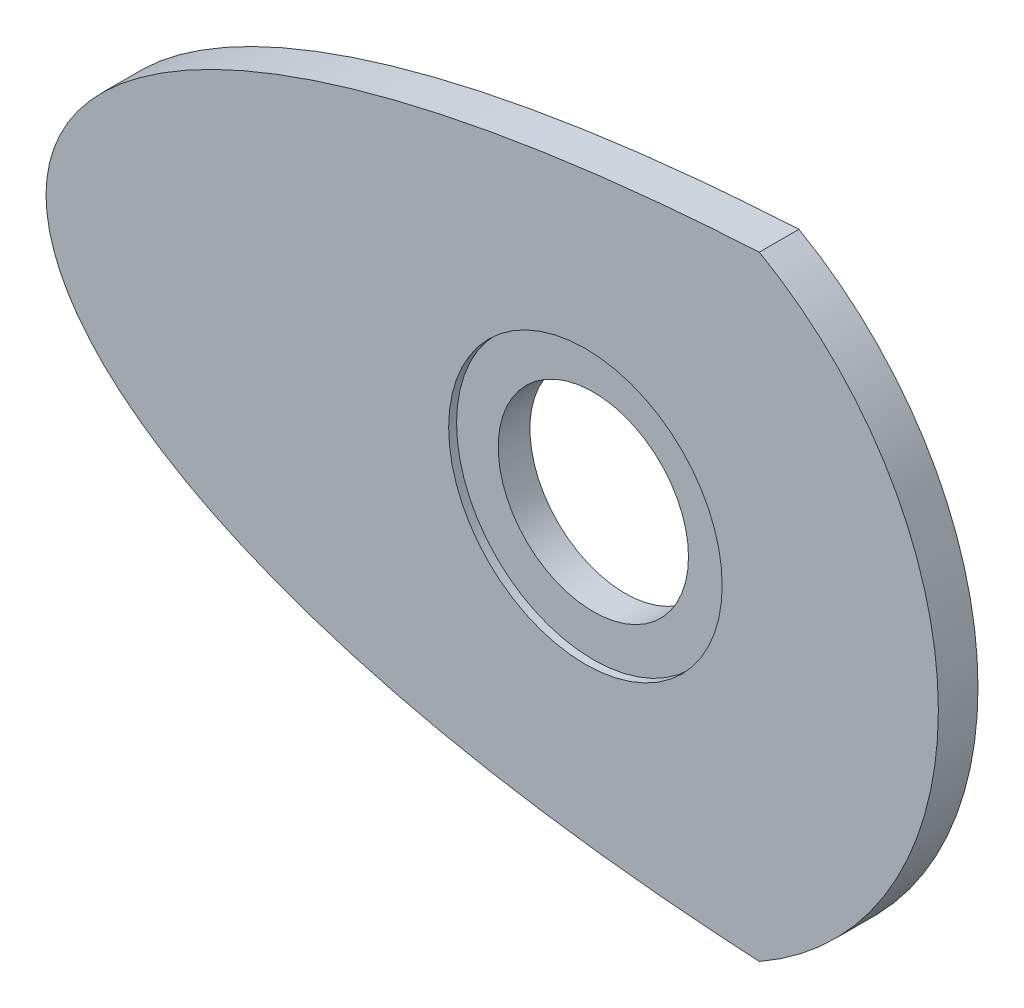
SolidWorks part; units mm, degrees
material "ABS"
ref_plane "Front Plane" through (0, 0, 0) normal (0, 0, 1) x (1, 0, 0)
ref_plane "Top Plane" through (0, 0, 0) normal (0, 1, 0) x (1, 0, 0)
ref_plane "Right Plane" through (0, 0, 0) normal (1, 0, 0) x (0, 0, -1)
sketch "Sketch1" plane through (0, 0, 0) normal (0, 0, 1) x (1, 0, 0)
  line L0 (-115.3, 26.8948) -> (-172.4748, 26.8948) construction
  circle A21 centre (-137.9144, 26.8948) radius 6.096
  circle A22 centre (-159.0811, 26.8948) radius 4.2333
  arc A23 (-126.7727, 46.574) -> (-126.7727, 7.2155) centre (-137.9144, 26.8948) cw
  spline S0 degree 3 poles (-172.4748, 26.8948) (-172.4738, 26.5585) (-172.4197, 25.7223) (-172.0978, 24.2517) (-171.3058, 22.4195) (-169.8894, 20.3904) (-167.7999, 18.3231) (-165.0585, 16.3272) (-161.7116, 14.468) (-157.8092, 12.7833) (-153.3985, 11.2954) (-148.5237, 10.0176) (-143.226, 8.9573) (-137.5444, 8.118) (-132.0171, 7.5506) (-128.3867, 7.3035) (-126.7727, 7.2155) knots 0.5 0.5 0.5 0.5 0.502167 0.50539 0.509656 0.514948 0.521245 0.528521 0.536745 0.545881 0.555891 0.56673 0.578353 0.59071 0.603747 0.614169 0.614169 0.614169 0.614169
  spline S1 degree 3 poles (-172.4748, 26.8948) (-172.4738, 27.231) (-172.4197, 28.0672) (-172.0978, 29.5379) (-171.3058, 31.37) (-169.8894, 33.3991) (-167.7999, 35.4664) (-165.0585, 37.4623) (-161.7116, 39.3215) (-157.8092, 41.0062) (-153.3985, 42.4941) (-148.5237, 43.7719) (-143.226, 44.8322) (-137.5444, 45.6715) (-132.0171, 46.2389) (-128.3867, 46.486) (-126.7727, 46.574) knots 0.5 0.5 0.5 0.5 0.502167 0.50539 0.509656 0.514948 0.521245 0.528521 0.536745 0.545881 0.555891 0.56673 0.578353 0.59071 0.603747 0.614169 0.614169 0.614169 0.614169
  dimension "D2" = 21.1667
  dimension "D1" = 12.192
extrude "Boss-Extrude2" add sketch "Sketch1" along normal blind 2.54 contours L0 A22 | A22 L0 | A23 L0 A21 A22 S0 | L0 A21 | A21 L0 | L0 A23 S1 A22 A21 region at (-141.2091, 18.1481, 0) region at (-141.2091, 35.6414, 0) region at (-137.9144, 24.3075, 0) region at (-137.9144, 29.482, 0) region at (-159.0811, 25.0981, 0) region at (-159.0811, 28.6914, 0)
extrude "Boss-Extrude3" add sketch "Sketch1<5>" against normal blind 7.62 contours A22 L0 | L0 A22 | A22 region at (-159.0811, 25.0981, 0) region at (-159.0811, 28.6914, 0)
sketch "Sketch1<5>" plane through (0, 0, 0) normal (0, 0, 1) x (1, 0, 0) same geometry as "Sketch1"
extrude "Cut-Extrude1" cut sketch "Sketch1<6>" along normal through all contours A21
sketch "Sketch1<6>" plane through (0, 0, 0) normal (0, 0, 1) x (1, 0, 0) same geometry as "Sketch1"
sketch "Sketch4" plane through (0, 0, 2.54) normal (0, 0, 1) x (1, 0, 0)
  arc A1 (-126.7727, 7.2155) -> (-126.7727, 46.574) centre (-137.9144, 26.8948) ccw
  arc A2 (-126.7727, 7.2155) -> (-126.7727, 46.574) centre (-137.9144, 26.8948) ccw
  circle A3 centre (-137.9144, 26.8948) radius 8.763
  spline S2 degree 3 poles (-870.5641, 3950.707) (283.2061, -274.5528) (59.1321, 65.8604) (-137.5444, 45.6715) (-143.226, 44.8322) (-148.5237, 43.7719) (-153.3985, 42.4941) (-157.8092, 41.0062) (-161.7116, 39.3215) (-165.0585, 37.4623) (-167.7999, 35.4664) (-169.8894, 33.3991) (-171.3058, 31.37) (-172.0978, 29.5379) (-180.8265, -10.3323) (97.3905, -84.506) (1357.2668, 3709.0209) knots -0.738604 -0.738604 -0.738604 -0.738604 0.510422 0.523459 0.535816 0.547438 0.558278 0.568287 0.577424 0.585648 0.592924 0.599221 0.604513 0.608778 0.612002 0.866295 0.866295 0.866295 0.866295 only from (-126.7727, 46.574) to (-172.4748, 26.8948)
  spline S3 degree 3 poles (1357.3121, -3655.3679) (97.397, 138.2973) (-180.8266, 64.1222) (-172.0978, 24.2517) (-171.3058, 22.4195) (-169.8894, 20.3904) (-167.7999, 18.3231) (-165.0585, 16.3272) (-161.7116, 14.468) (-157.8092, 12.7833) (-153.3985, 11.2954) (-148.5237, 10.0176) (-143.226, 8.9573) (-137.5444, 8.118) (59.1319, -12.0709) (283.2057, 328.3417) (-870.561, -3896.9063) knots 0.24787 0.24787 0.24787 0.24787 0.502167 0.50539 0.509656 0.514948 0.521245 0.528521 0.536745 0.545881 0.555891 0.56673 0.578353 0.59071 0.603747 1.852772 1.852772 1.852772 1.852772 only from (-172.4748, 26.8948) to (-126.7727, 7.2155)
  spline S4 degree 3 poles (-126.7727, 46.574) (-128.3867, 46.486) (-132.0171, 46.2389) (-137.5444, 45.6715) (-143.226, 44.8322) (-148.5237, 43.7719) (-153.3985, 42.4941) (-157.8092, 41.0062) (-161.7116, 39.3215) (-165.0585, 37.4623) (-167.7999, 35.4664) (-169.8894, 33.3991) (-171.3058, 31.37) (-172.0978, 29.5379) (-172.4197, 28.0672) (-172.4738, 27.231) (-172.4748, 26.8948) knots 0.5 0.5 0.5 0.5 0.510422 0.523459 0.535816 0.547438 0.558278 0.568287 0.577424 0.585648 0.592924 0.599221 0.604513 0.608778 0.612002 0.614169 0.614169 0.614169 0.614169
  spline S5 degree 3 poles (-172.4748, 26.8948) (-172.4738, 26.5585) (-172.4197, 25.7223) (-172.0978, 24.2517) (-171.3058, 22.4195) (-169.8894, 20.3904) (-167.7999, 18.3231) (-165.0585, 16.3272) (-161.7116, 14.468) (-157.8092, 12.7833) (-153.3985, 11.2954) (-148.5237, 10.0176) (-143.226, 8.9573) (-137.5444, 8.118) (-132.0171, 7.5506) (-128.3867, 7.3035) (-126.7727, 7.2155) knots 0.5 0.5 0.5 0.5 0.502167 0.50539 0.509656 0.514948 0.521245 0.528521 0.536745 0.545881 0.555891 0.56673 0.578353 0.59071 0.603747 0.614169 0.614169 0.614169 0.614169
  dimension "D2" = 17.526
  dimension "D1" = 0
extrude "Cut-Extrude2" cut sketch "Sketch4" against normal blind 0.508 contours A3
